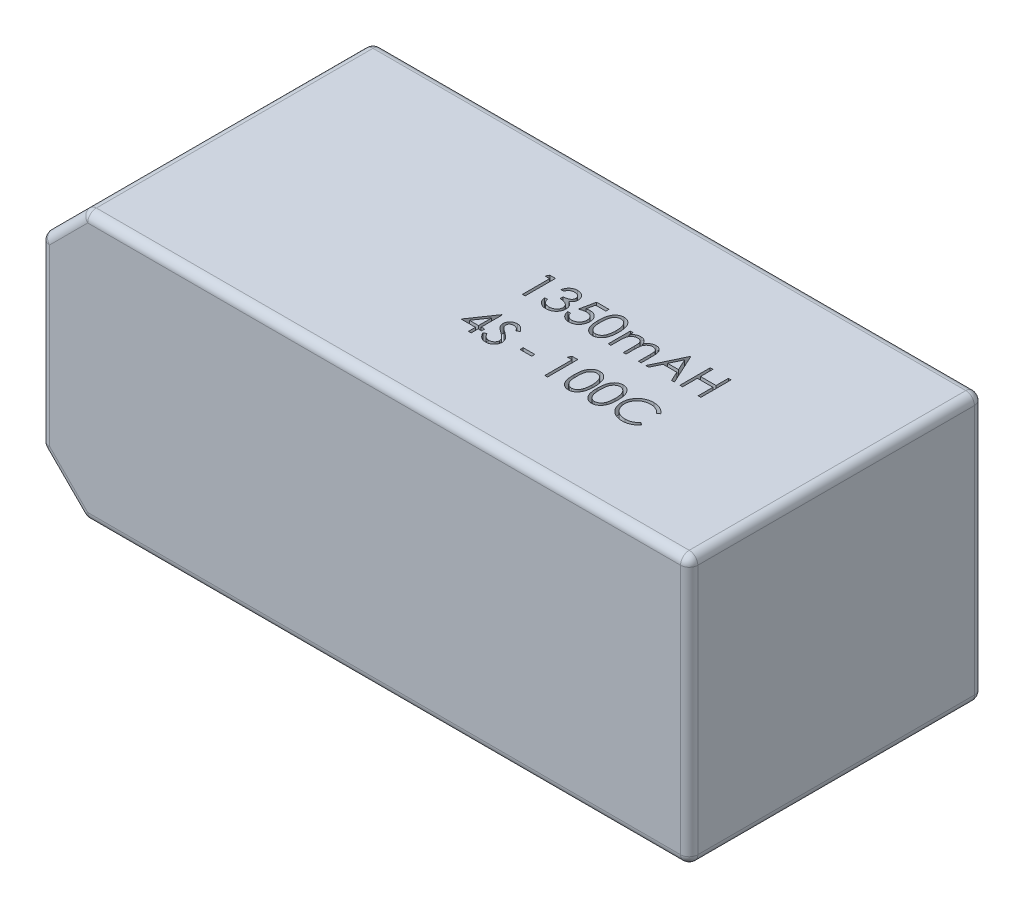
SolidWorks part; units mm, degrees
ref_plane "Front Plane" through (0, 0, 0) normal (0, 0, 1) x (1, 0, 0)
ref_plane "Top Plane" through (0, 0, 0) normal (0, 1, 0) x (1, 0, 0)
ref_plane "Right Plane" through (0, 0, 0) normal (1, 0, 0) x (0, 0, -1)
sketch "Sketch1" plane through (0, 0, 0) normal (0, 1, 0) x (1, 0, 0)
  line L1 (-37.5, -17) -> (37.5, -17)
  line L2 (-37.5, -17) -> (-37.5, 17)
  line L3 (-37.5, 17) -> (37.5, 17)
  line L4 (37.5, -17) -> (37.5, 17)
  line L5 (-37.5, -17) -> (37.5, 17) construction
  line L6 (-37.5, 17) -> (37.5, -17) construction
  point P0 (0, 0)
  dimension "D1" = 75
  dimension "D2" = 34
extrude "Boss-Extrude1" add sketch "Sketch1" along normal mid plane 31
chamfer "Chamfer1" distance 5 angle 45 2 edges at (-37.5, 15.5, 0) (-37.5, -15.5, 0)
fillet "Fillet1" radius 1 18 edges at (37.5, -15.5, 0) (37.5, 15.5, 0) (-35, -13, -17) (-37.5, 0, -17) (-35, 13, -17) (2.5, -15.5, -17) (37.5, 0, -17) (2.5, 15.5, -17) (-35, -13, 17) (-37.5, 0, 17) (-35, 13, 17) (37.5, 0, 17) (2.5, 15.5, 17) (2.5, -15.5, 17) (-32.5, -15.5, 0) (-37.5, -10.5, 0) (-32.5, 15.5, 0) (-37.5, 10.5, 0)
sketch "Sketch2" plane through (0, 15.5, 0) normal (0, 1, 0) x (1, 0, 0)
  text T0 "1350mAH\r\n4S - 100C"
  point P1 (-12.6739, 5.391)
  point P2 (0, 0)
extrude "Cut-Extrude1" cut sketch "Sketch2" against normal blind 1
